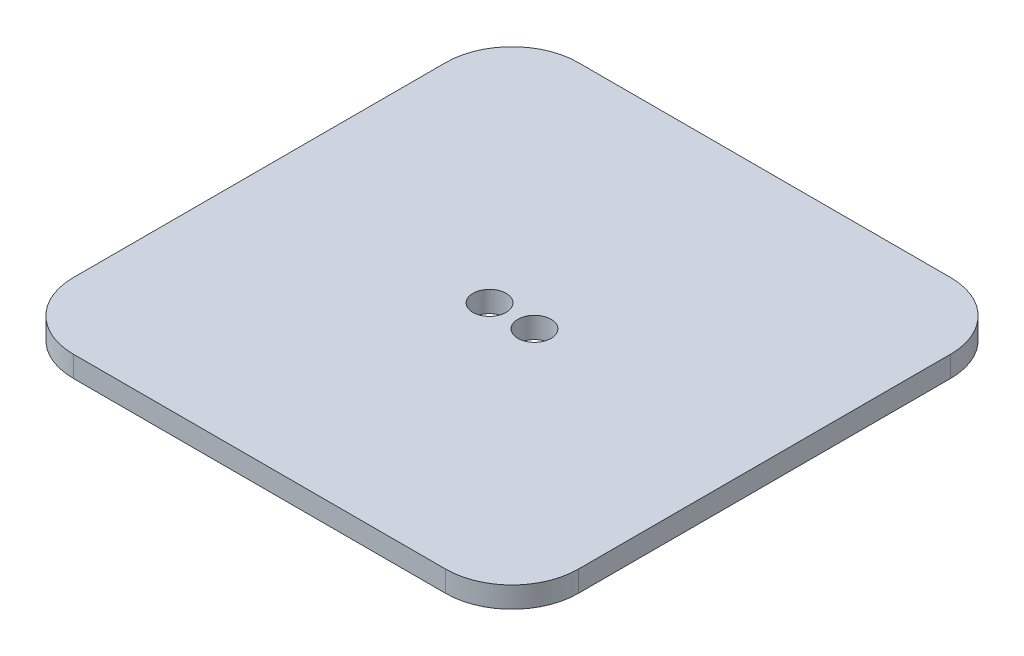
SolidWorks part; units mm, degrees
ref_plane "Front Plane" through (0, 0, 0) normal (0, 0, 1) x (1, 0, 0)
ref_plane "Top Plane" through (0, 0, 0) normal (0, 1, 0) x (1, 0, 0)
ref_plane "Right Plane" through (0, 0, 0) normal (1, 0, 0) x (0, 0, -1)
sketch "Sketch1" plane through (0, 0, 0) normal (0, 1, 0) x (1, 0, 0)
  line L1 (-38.1, -38.1) -> (38.1, -38.1)
  line L2 (-38.1, -38.1) -> (-38.1, 38.1)
  line L3 (-38.1, 38.1) -> (38.1, 38.1)
  line L4 (38.1, -38.1) -> (38.1, 38.1)
  line L5 (-38.1, -38.1) -> (38.1, 38.1) construction
  line L6 (-38.1, 38.1) -> (38.1, -38.1) construction
  point P0 (0, 0)
  dimension "D1" = 76.2
  dimension "D2" = 76.2
extrude "Boss-Extrude1" add sketch "Sketch1" along normal blind 3.175
fillet "Fillet1" radius 10 1 edges at (-38.1, 1.5875, 38.1)
fillet "Fillet2" radius 10 1 edges at (-38.1, 1.5875, -38.1)
fillet "Fillet3" radius 10 1 edges at (38.1, 1.5875, -38.1)
fillet "Fillet4" radius 10 1 edges at (38.1, 1.5875, 38.1)
sketch "Sketch2" plane through (0, 3.175, 0) normal (0, 1, 0) x (1, 0, 0)
  line L0 (-1.7463, 0) -> (1.7463, 0) construction
  line L1 (38.1, -28.1) -> (38.1, 28.1) construction
  circle A0 centre (3.3909, 0) radius 2.5
  circle A1 centre (-3.3909, 0) radius 2.5
  dimension "D1" = 5
  dimension "D2" = 5
  dimension "D3" = 6.7818
  dimension "D4" = 34.7091
extrude "Cut-Extrude1" cut sketch "Sketch2" against normal through all
